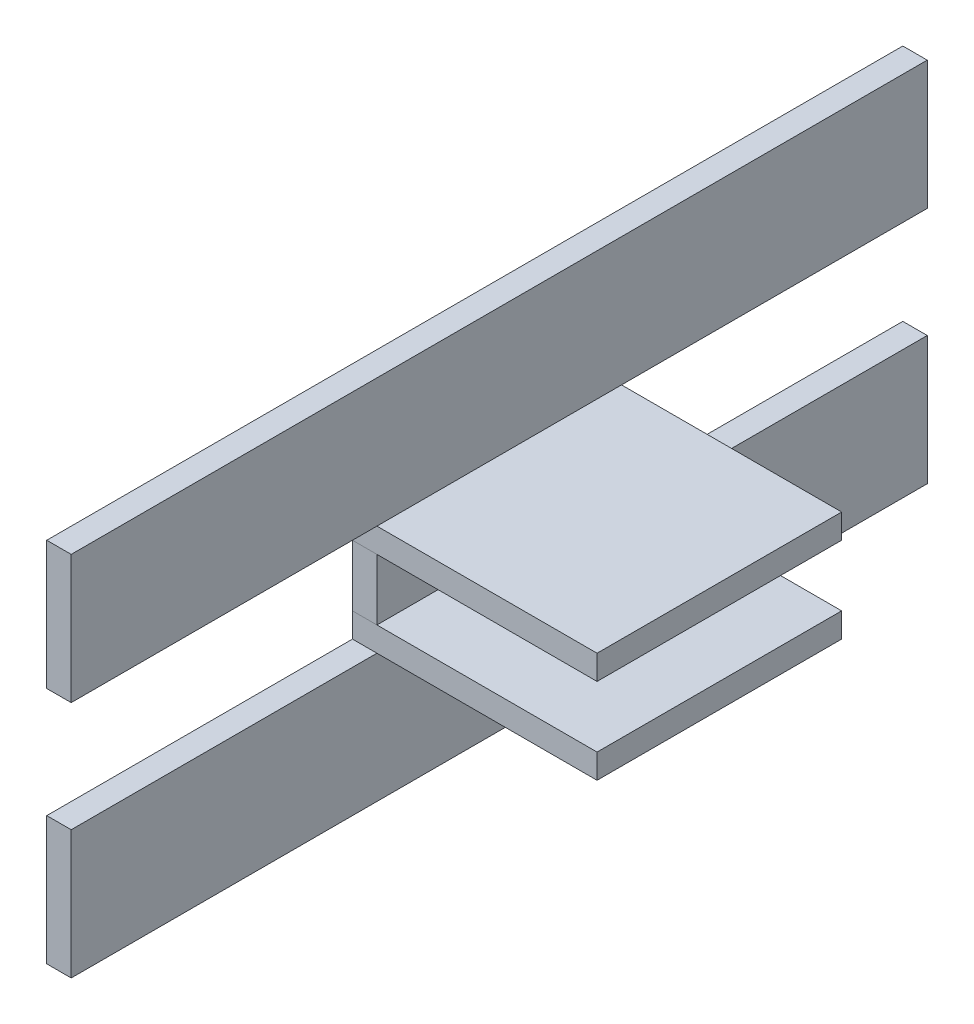
SolidWorks part; units mm, degrees
note: The reader was unsure of these and kept them because the rebuilt part matched: shared geometry of "Sketch1<4>".
ref_plane "Front Plane" through (0, 0, 0) normal (0, 0, 1) x (1, 0, 0)
ref_plane "Top Plane" through (0, 0, 0) normal (0, 1, 0) x (1, 0, 0)
ref_plane "Right Plane" through (0, 0, 0) normal (1, 0, 0) x (0, 0, -1)
sketch "Sketch1" plane through (0, 0, 0) normal (1, 0, 0) x (0, 0, -1)
  line L1 (0, 30) -> (70, 30)
  line L2 (0, 30) -> (0, 0)
  line L3 (0, 0) -> (70, 0)
  line L4 (70, 30) -> (70, 0)
  line L5 (0, 17.5) -> (70, 17.5)
  line L6 (0, 17.5) -> (0, 12.5)
  line L7 (0, 12.5) -> (70, 12.5)
  line L8 (70, 17.5) -> (70, 12.5)
  line L9 (0, 17.5) -> (70, 17.5)
  line L10 (0, 17.5) -> (0, 19.5)
  line L11 (0, 19.5) -> (70, 19.5)
  line L12 (70, 17.5) -> (70, 19.5)
  line L13 (70, 12.5) -> (0, 12.5)
  line L14 (70, 12.5) -> (70, 10.5)
  line L15 (70, 10.5) -> (0, 10.5)
  line L16 (0, 12.5) -> (0, 10.5)
  line L17 (0, 10.5) -> (25, 10.5)
  line L18 (0, 10.5) -> (0, 19.5)
  line L19 (0, 19.5) -> (25, 19.5)
  line L20 (25, 10.5) -> (25, 19.5)
  line L21 (70, 19.5) -> (45, 19.5)
  line L22 (70, 19.5) -> (70, 10.5)
  line L23 (70, 10.5) -> (45, 10.5)
  line L24 (45, 19.5) -> (45, 10.5)
  dimension "D1" = 5
  dimension "D2" = 30
  dimension "D3" = 12.5
  dimension "D4" = 70
  dimension "D5" = 2
  dimension "D6" = 2
  dimension "D7" = 20
  dimension "D8" = 25
extrude "Boss-Extrude1" add sketch "Sketch1" along normal blind 2 contours L2 L5 L4 L1 | L7 L2 L3 L4 | L2 L7 L4 L5
extrude "Boss-Extrude2" add sketch "Sketch1<4>" along normal blind 20 contours L15 L4 L7 L2 | L11 L2 L5 L4
sketch "Sketch1<4>" plane through (0, 0, 0) normal (1, 0, 0) x (0, 0, -1) same geometry as "Sketch1"
